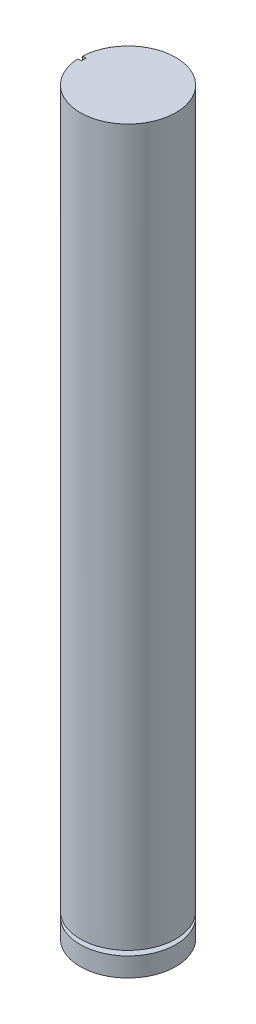
SolidWorks part; units mm, degrees
ref_plane "Front Plane" through (0, 0, 0) normal (0, 0, 1) x (1, 0, 0)
ref_plane "Top Plane" through (0, 0, 0) normal (0, 1, 0) x (1, 0, 0)
ref_plane "Right Plane" through (0, 0, 0) normal (1, 0, 0) x (0, 0, -1)
sketch "Sketch1" plane through (0, 0, 0) normal (0, 1, 0) x (1, 0, 0)
  circle A0 centre (0, 0) radius 2
  dimension "D1" = 4
extrude "Boss-Extrude1" add sketch "Sketch1" along normal blind 30.9292
sketch "Sketch2" plane through (0, 0, 0) normal (1, 0, 0) x (0, 0, -1)
  line L0 (2, 0) -> (2, 30.9292) construction
  line L1 (2, 1) -> (1.5, 1)
  line L2 (2, 1) -> (2, 0.8)
  line L3 (2, 0.8) -> (1.5, 0.8)
  line L4 (1.5, 1) -> (1.5, 0.8)
  line L5 (-2, 0) -> (2, 0) construction
  line L6 (0, 0) -> (0, 4.8308) construction
  dimension "D1" = 0.5
  dimension "D2" = 0.2
  dimension "D3" = 0.8
revolve "Cut-Revolve1" cut sketch "Sketch2" angle 360 about L6
sketch "Sketch3" plane through (0, 30.9292, 0) normal (0, 1, 0) x (1, 0, 0)
  line L0 (0, 0) -> (-2, 0) construction
  line L2 (-2, 0.1) -> (-1.85, 0.1)
  line L3 (-2, 0.1) -> (-2, -0.1)
  line L4 (-2, -0.1) -> (-1.85, -0.1)
  line L5 (-1.85, 0.1) -> (-1.85, -0.1)
  circle A0 centre (0, 0) radius 2 construction
  dimension "D1" = 0.2
  dimension "D2" = 0.15
extrude "Cut-Extrude1" cut sketch "Sketch3" against normal blind 3
